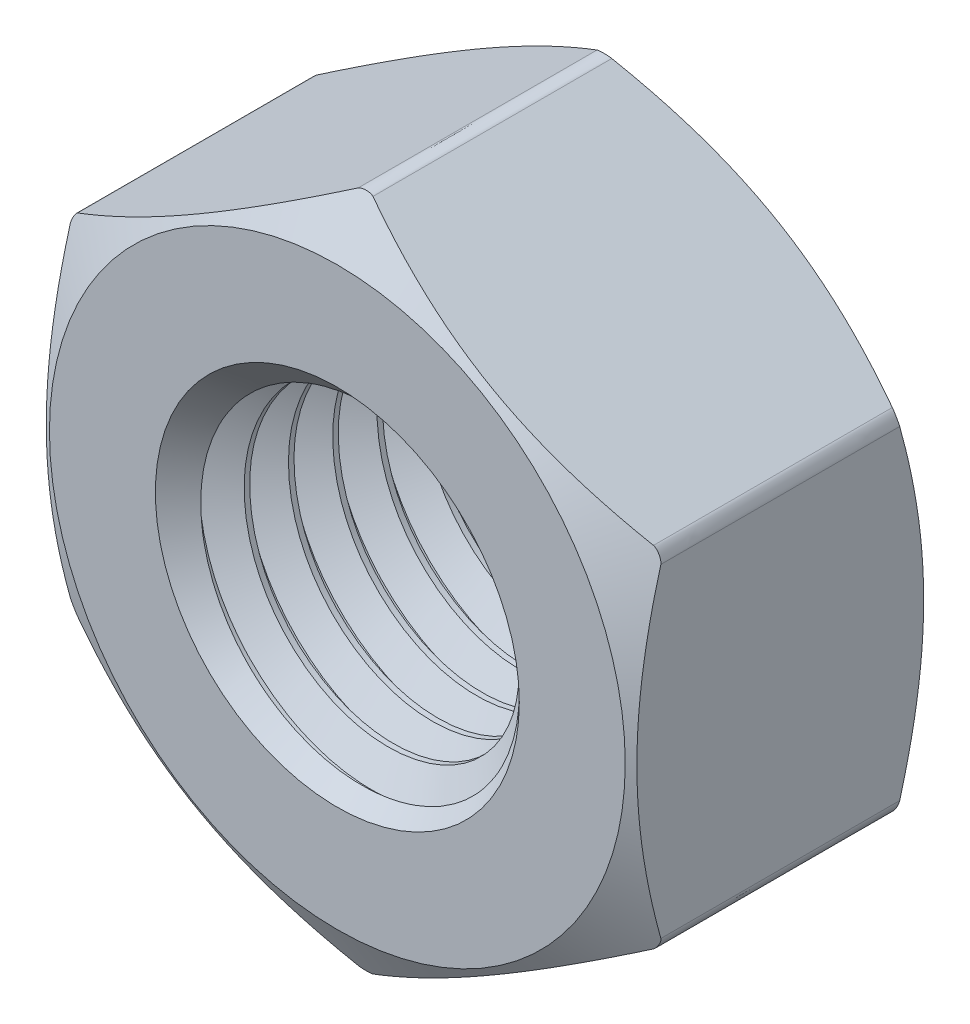
SolidWorks part; units mm, degrees
ref_plane "Front Plane" through (0, 0, 0) normal (0, 0, 1) x (1, 0, 0)
ref_plane "Top Plane" through (0, 0, 0) normal (0, 1, 0) x (1, 0, 0)
ref_plane "Right Plane" through (0, 0, 0) normal (1, 0, 0) x (0, 0, -1)
sketch "Sketch1" plane through (0, 0, 0) normal (0, 0, 1) x (1, 0, 0)
  line L0 (0, -5.7735) -> (0, 5.7735) construction
  line L1 (0, -5.7735) -> (5, -2.8868) construction
  line L2 (5, -2.8868) -> (5, 2.8868) construction
  line L3 (5, 2.8868) -> (0, 5.7735) construction
  line L4 (0, 5.7735) -> (-5, 2.8868) construction
  line L5 (-5, 2.8868) -> (-5, -2.8868) construction
  line L6 (-5, -2.8868) -> (0, -5.7735) construction
  line L7 (-5, 0) -> (5, 0) construction
  line L8 (0, 0) -> (1.5, -2.5981) construction
  circle A0 centre (0, 0) radius 5 construction
  circle A1 centre (0, 0) radius 3 construction
  point P11 (0, 0)
  point P12 (0, -3)
  point P14 (3, 0)
  point P15 (0, 3)
  point P16 (-3, 0)
  point P19 (1.5, -2.5981)
  dimension "Thread Diameter" = 6
  dimension "Width" = 10
  dimension "D1" = 30
sketch "Sketch2" plane through (0, 0, 0) normal (1, 0, 0) x (0, 0, -1)
  line L0 (0, -5) -> (0, 5) construction
  line L1 (-2.5, 5) -> (2.5, 5) construction
  line L2 (-2.5, 5) -> (-2.5, -5) construction
  line L3 (-2.5, -5) -> (2.5, -5) construction
  line L4 (2.5, 5) -> (2.5, -5) construction
  line L5 (2.5, 0) -> (-2.5, 0) construction
  line L8 (-2.5, 3) -> (2.5, 3) construction
  line L9 (-2.5, -3) -> (2.5, -3) construction
  line L10 (-3.2031, 3.0812) -> (-2.4531, 3.0812) construction
  line L11 (-2.4531, 3.0812) -> (-2.8281, 2.4317) construction
  line L12 (-2.8281, 2.4317) -> (-3.2031, 3.0812) construction
  line L13 (-3.1797, 3.0406) -> (-2.4766, 3.0406) construction
  line L14 (-3.1563, 3) -> (-2.5, 3) construction
  line L15 (-2.875, 2.5129) -> (-2.7813, 2.5129) construction
  line L16 (-2.8281, 2.5129) -> (-2.8281, 2.4317) construction
  line L17 (-2.8281, 3.0812) -> (-2.8281, 3) construction
  point P8 (0, 0)
  point P29 (-2.8281, 3.0406)
  dimension "Height" = 5
  dimension "Thread Pitch" = 0.75
  dimension "D2" = 0.0938
sketch "Sketch3" plane through (0, 0, 0) normal (0, 0, 1) x (1, 0, 0)
  line L1 (0, -5.7735) -> (5, -2.8868)
  line L2 (5, -2.8868) -> (5, 2.8868)
  line L3 (5, 2.8868) -> (0, 5.7735)
  line L4 (0, 5.7735) -> (-5, 2.8868)
  line L5 (-5, 2.8868) -> (-5, -2.8868)
  line L6 (-5, -2.8868) -> (0, -5.7735)
  circle A0 centre (0, 0) radius 5 construction
  circle A1 centre (0, 0) radius 2.5129
extrude "Boss-Extrude1" add sketch "Sketch3" along normal up to vertex (2.5 mm away) and the other way up to vertex (2.5 mm away) up to point (0, 0, 2.5) other way up to point (0, 0, -2.5)
sketch "Sketch4" plane through (0, 0, 0) normal (0, 0, 1) x (1, 0, 0)
  circle A0 centre (0, 0) radius 4.875
  dimension "D1" = 9.75
extrude "Cut-Extrude1" cut sketch "Sketch4" against normal through all draft 60 from vertex flip side to cut starting at point (0, 0, 2.5)
extrude "Cut-Extrude2" cut sketch "Sketch4<2>" along normal through all draft 60 from vertex flip side to cut starting at point (0, 0, -2.5)
sketch "Sketch4<2>" plane through (0, 0, 0) normal (0, 0, 1) x (1, 0, 0) same geometry as "Sketch4"
chamfer "Chamfer1" distance 0.4688 angle 45 2 edges at (2.5129, 0, -2.5) (2.5129, 0, 2.5)
fillet "Fillet1" radius 0.25 6 edges at (-5, -2.8868, 0) (-5, 2.8868, 0) (0, -5.7735, 0) (5, -2.8868, 0) (0, 5.7735, 0) (5, 2.8868, 0) conic rho 0.3
ref_axis "Center Axis 1" through (0, 0, -16.7332) along (0, 0, 1)
sketch "Sketch5" plane through (0, 0, 0) normal (0, 0, 1) x (1, 0, 0)
  circle A0 centre (0, 0) radius 3 construction
  circle A1 centre (0, 0) radius 3
extrude "Cut-Extrude3" cut sketch "Sketch5" against normal through all both and the other way through all
sketch "Sketch6" plane through (0, 0, 2.5) normal (0, 0, 1) x (1, 0, 0)
  circle A0 centre (0, 0) radius 3 construction
  circle A1 centre (0, 0) radius 3
curve "Helix/Spiral1" pitch 0.75 height 5.75 radius 3 centre (0, 0, 2.5) axis (0, 0, -1) start towards (0, 1, 0)
sketch "Sketch7" plane through (0, 0, 0) normal (1, 0, 0) x (0, 0, -1)
  line L0 (-3.1797, 3.0406) -> (-2.4766, 3.0406)
  line L1 (-2.4766, 3.0406) -> (-2.7813, 2.5129)
  line L2 (-2.7813, 2.5129) -> (-2.875, 2.5129)
  line L3 (-2.875, 2.5129) -> (-3.1797, 3.0406)
sweep "Sweep1" add profiles "Sketch7" path "Helix/Spiral1"
sketch "Sketch8" plane through (0, 0, 2.5) normal (0, 0, 1) x (1, 0, 0)
  circle A0 centre (0, 0) radius 3.0812
extrude "Cut-Extrude4" cut sketch "Sketch8" against normal through all draft 45 and the other way through all
sketch "Sketch9" plane through (0, 0, -2.5) normal (0, 0, -1) x (-1, 0, 0)
  circle A1 centre (0, 0) radius 3.0812
  circle A2 centre (0, 0) radius 3.0812
  dimension "D1" = 0
extrude "Cut-Extrude5" cut sketch "Sketch9" against normal through all draft 45 and the other way through all
equation "\"D2@Sketch2\" = \"Thread Pitch@Sketch2\" / 8"
equation "\"D1@Chamfer1\"=\"Thread Pitch@Sketch2\"*.625"
equation "\"D1@Sketch4\"=\"Width@Sketch1\"*.975"
equation "\"D1@Fillet1\"=\"Width@Sketch1\"*.025"
equation "\"D4@Helix/Spiral1\"=\"Thread Pitch@Sketch2\""
equation "\"D3@Helix/Spiral1\"=\"Height@Sketch2\"+\"Thread Pitch@Sketch2\""
equation "\"D3@Cut-Extrude2\"=\"D3@Cut-Extrude1\""
